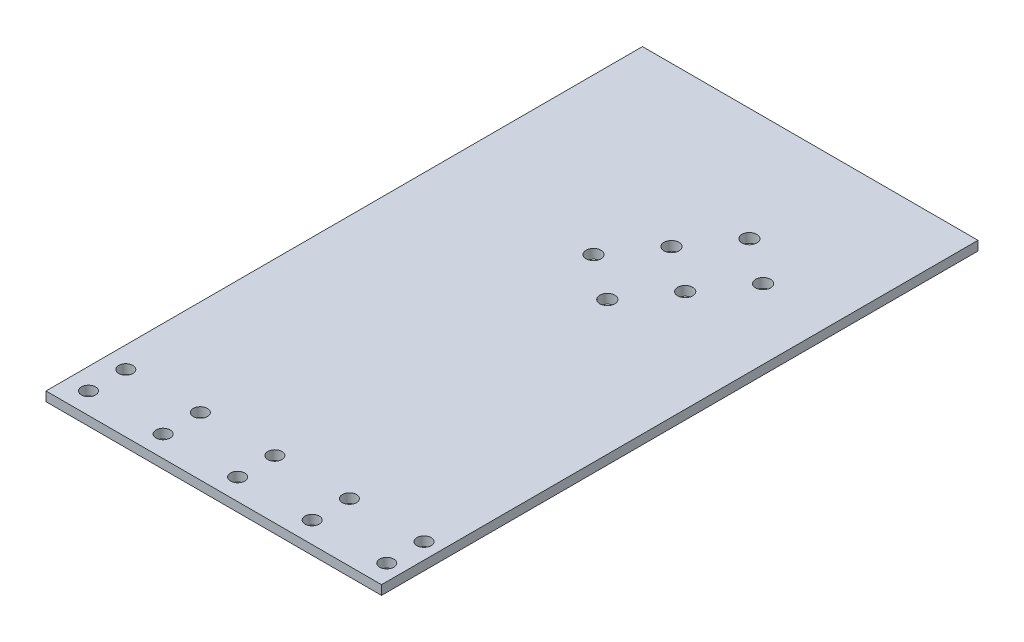
SolidWorks part; units mm, degrees
material "6061-T6 (SS)"
ref_plane "Front Plane" through (0, 0, 0) normal (0, 0, 1) x (1, 0, 0)
ref_plane "Top Plane" through (0, 0, 0) normal (0, 1, 0) x (1, 0, 0)
ref_plane "Right Plane" through (0, 0, 0) normal (1, 0, 0) x (0, 0, -1)
sketch "Sketch1" plane through (0, 0, 0) normal (0, 1, 0) x (1, 0, 0)
  line L5 (0, 0) -> (114.3, 0)
  line L6 (0, 0) -> (0, 203.2)
  line L7 (0, 203.2) -> (114.3, 203.2)
  line L8 (114.3, 0) -> (114.3, 203.2)
  dimension "D1" = 203.2
  dimension "D2" = 114.3
extrude "Boss-Extrude1" add sketch "Sketch1" along normal blind 3.175
sketch "Sketch2" plane through (0, 3.175, 0) normal (0, 1, 0) x (1, 0, 0)
  line L0 (0, 0) -> (114.3, 0) construction
  line L1 (0, 203.2) -> (0, 0) construction
  circle A0 centre (7.239, 7.239) radius 2.413
  circle A2 centre (7.239, 19.939) radius 2.413
  circle A3 centre (32.639, 19.939) radius 2.413
  circle A4 centre (58.039, 19.939) radius 2.413
  circle A5 centre (83.439, 19.939) radius 2.413
  circle A6 centre (108.839, 19.939) radius 2.413
  circle A7 centre (32.639, 7.239) radius 2.413
  circle A8 centre (58.039, 7.239) radius 2.413
  circle A9 centre (83.439, 7.239) radius 2.413
  circle A10 centre (108.839, 7.239) radius 2.413
  dimension "D1" = 4.826
  dimension "D2" = 7.239
  dimension "D3" = 7.239
  dimension "D4" = 2
  dimension "D5" = 5
extrude "Cut-Extrude1" cut sketch "Sketch2" against normal through all
sketch "Sketch3" plane through (0, 3.175, 0) normal (0, 1, 0) x (1, 0, 0)
  circle A0 centre (74.8762, 164.7314) radius 2.5527
  circle A1 centre (74.8762, 164.7314) radius 2.5527 construction
  circle A2 centre (90.481, 153.8048) radius 2.5527
  circle A3 centre (90.481, 153.8048) radius 2.5527 construction
  circle A4 centre (63.9496, 149.1265) radius 2.5527
  circle A5 centre (79.5544, 138.1999) radius 2.5527
  circle A6 centre (53.0229, 133.5217) radius 2.5527
  circle A7 centre (68.6278, 122.5951) radius 2.5527
  dimension "D1" = 5.1054
  dimension "D2" = 5.1054
  dimension "D4" = 19.05
  dimension "D3" = 3
extrude "Cut-Extrude2" cut sketch "Sketch3" against normal through all
